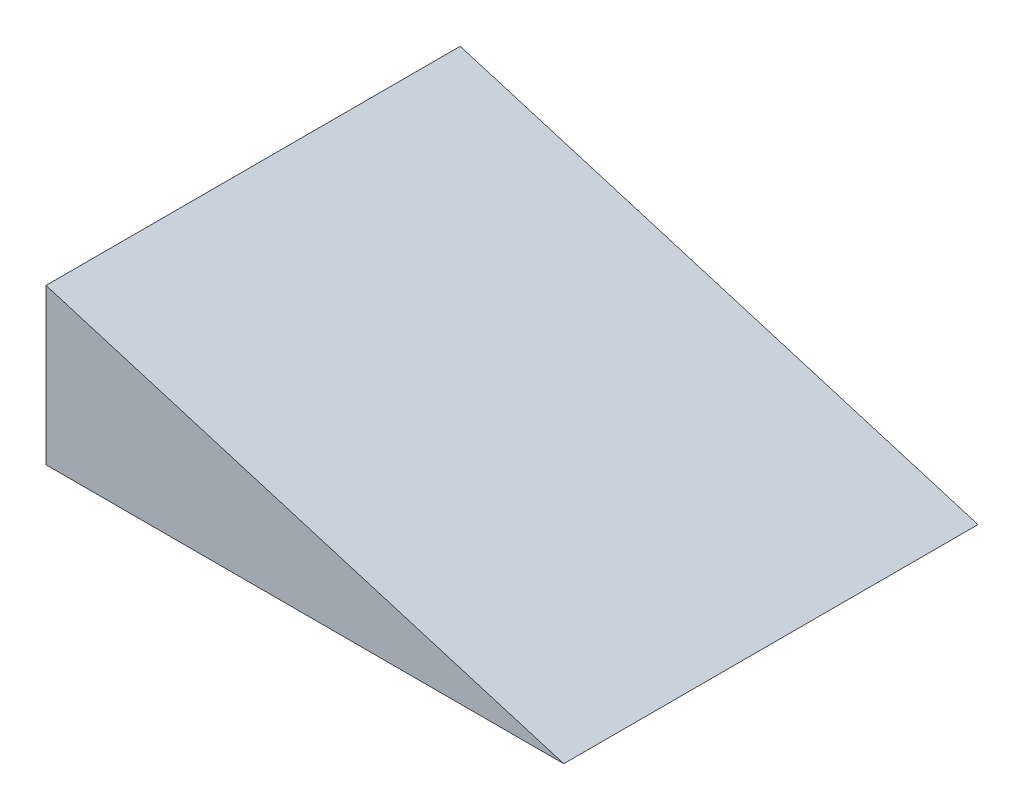
SolidWorks part; units mm, degrees
material "Balsa"
ref_plane "Front Plane" through (0, 0, 0) normal (0, 0, 1) x (1, 0, 0)
ref_plane "Top Plane" through (0, 0, 0) normal (0, 1, 0) x (1, 0, 0)
ref_plane "Right Plane" through (0, 0, 0) normal (1, 0, 0) x (0, 0, -1)
sketch "Sketch1" plane through (0, 0, 0) normal (0, 0, 1) x (1, 0, 0)
  line L0 (0, 228.6) -> (0, 0)
  line L1 (0, 0) -> (762, 0)
  line L2 (762, 0) -> (0, 228.6)
  dimension "D1" = 762
  dimension "D2" = 228.6
extrude "Boss-Extrude1" add sketch "Sketch1" against normal blind 609.6
shell "Shell1" thickness 9.525 removed face at (0, 114.3, -304.8)
sketch "Sketch2" plane through (62.9174, 209.7248, 0) normal (0.2873, 0.9578, 0) x (0.9578, -0.2873, 0)
  line L1 (-65.6877, 609.6) -> (729.8636, 609.6)
  line L2 (-65.6877, 609.6) -> (-65.6877, 0)
  line L3 (-65.6877, 0) -> (729.8636, 0)
  line L4 (729.8636, 609.6) -> (729.8636, 0)
